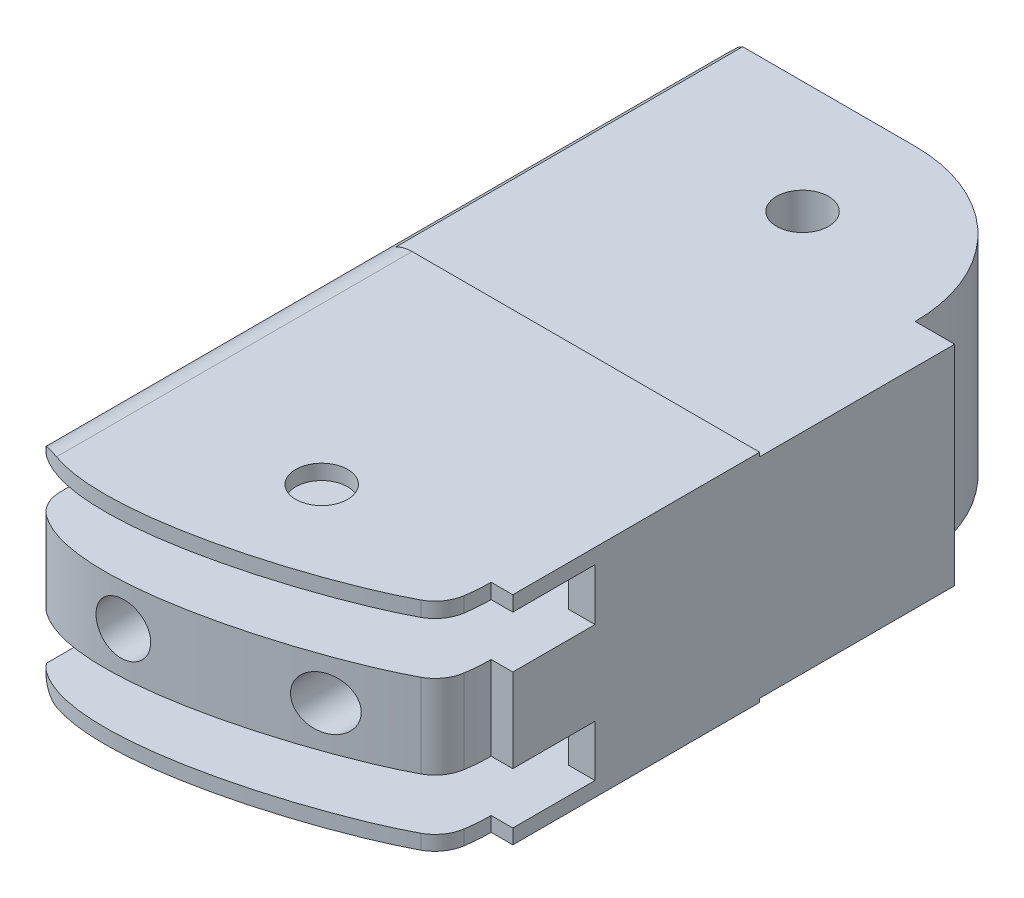
SolidWorks part; units mm, degrees
ref_plane "Front Plane" through (0, 0, 0) normal (0, 0, 1) x (1, 0, 0)
ref_plane "Top Plane" through (0, 0, 0) normal (0, 1, 0) x (1, 0, 0)
ref_plane "Right Plane" through (0, 0, 0) normal (1, 0, 0) x (0, 0, -1)
sketch "Sketch1" plane through (0, 0, 0) normal (0, 0, 1) x (1, 0, 0)
  line L0 (-24.2561, -24.0702) -> (-22.0061, -24.0702) construction
  line L1 (-24.2561, -17.8202) -> (-2.2017, -17.8202)
  line L2 (-24.2561, -17.8202) -> (-24.2561, -30.3202)
  line L3 (-24.2561, -30.3202) -> (-2.2017, -30.3202)
  line L4 (-2.2017, -17.8202) -> (-2.2017, -30.3202)
  line L5 (-2.2017, -24.0702) -> (-4.4517, -24.0702) construction
  line L6 (-22.0061, -24.0702) -> (-22.0061, -30.3202) construction
  line L7 (-4.4517, -24.0702) -> (-4.4517, -30.3202) construction
extrude "Boss-Extrude1" add sketch "Sketch1" along normal blind 43
sketch "Sketch2" plane through (0, -30.3202, 0) normal (0, -1, 0) x (1, 0, 0)
  line L0 (-3.4524, 34.2429) -> (-2.2017, 34.2429)
  line L1 (-24.2561, 0) -> (-2.2017, 0) construction
  line L2 (-13.2289, 0) -> (-13.2289, 8.75) construction
  line L4 (-24.2561, 43) -> (-24.2561, 0) construction
  line L5 (-4.4789, 8.75) -> (-2.2017, 8.75)
  line L6 (-2.2017, 43) -> (-2.2017, 0) construction
  line L7 (-13.2289, 43) -> (-13.2289, 34.2429) construction
  line L8 (-24.2561, 43) -> (-2.2017, 43) construction
  line L11 (-13.2289, 8.75) -> (-13.2289, 6.5) construction
  line L12 (-24.2561, 0) -> (-2.2017, 0) construction
  arc A1 (-13.2289, 0) -> (-4.4789, 8.75) centre (-13.2289, 8.75) ccw
  circle A4 centre (-13.2289, 6.5) radius 1.5
  arc A6 (-3.4524, 34.2429) -> (-3.7578, 36.6675) centre (-13.2289, 34.2429) ccw
  circle A7 centre (-13.2289, 34.2429) radius 1.5
  spline S0 degree 3 poles (-2.2017, 8.75) (5.3921, 3.8803) (-0.7771, -4.5233) (-17.1743, -10.6233) (-34.8214, -0.026) (-24.2561, 8.75) knots 0 0 0 0 0.283273 0.504245 1 1 1 1
  spline S1 degree 3 poles (-24.2561, 33.8451) (-30.5755, 43.6074) (-11.1959, 55.0124) (11.4737, 42.1354) (-2.2017, 34.2429) knots 0 0 0 0 0.486113 1 1 1 1
  spline S2 degree 1 poles (-13.2289, 0) (-23.4906, 0) knots 0 0 1 1
  spline S3 degree 2 poles (-23.4906, 0) (-24.9665, 4.2378) (-24.2561, 8.75) knots 0 0 0 1 1 1
  spline S4 degree 3 poles (-3.7578, 36.6675) (-8.0593, 39.5101) (-28.6882, 46.07) (-24.2561, 33.8451) knots 0 0 0 0 1 1 1 1
extrude "Cut-Extrude1" cut sketch "Sketch2" against normal blind 15 and the other way blind 10
fillet "Fillet3" radius 2 4 edges at (-24.2561, -17.8202, 21.0415) (-24.2561, -30.3202, 21.0415) (-24.2561, -24.0702, 3.0015) (-24.2561, -24.0702, 39.0815)
ref_plane "Plane1" through (0, 0, 0) normal (0, 0, 1) x (1, 0, 0)
sketch "Sketch5" plane through (0, 0, 0) normal (0, 0, 1) x (1, 0, 0)
  line L0 (-2.2017, -24.0702) -> (-8.4468, -24.0702) construction
  line L1 (-2.2017, -30.3202) -> (-24.2561, -30.3202) construction
  line L2 (-2.2017, -30.3202) -> (-2.2017, -17.8202) construction
  line L3 (-2.2017, -17.8202) -> (-24.2561, -17.8202) construction
  line L4 (-24.2561, -30.3202) -> (-24.2561, -17.8202) construction
  line L5 (-24.2561, -24.0702) -> (-18.0111, -24.0702) construction
  circle A0 centre (-18.0111, -24.0702) radius 1.5
  circle A1 centre (-8.4468, -24.0702) radius 1.5
extrude "Cut-Extrude4" cut sketch "Sketch5" along normal through all
ref_plane "Plane5" through (0, 0, 38) normal (0, 0, 1) x (1, 0, 0)
sketch "Sketch16" plane through (0, 0, 38) normal (0, 0, 1) x (1, 0, 0)
  line L0 (-2.9534, -17.6304) -> (-2.1067, -18.6895) construction
  line L1 (-2.9534, -17.6304) -> (-24.3617, -17.6304) construction
  line L3 (-2.1067, -30.8303) -> (-24.3617, -30.8303) construction
  line L4 (-24.3617, -17.6304) -> (-24.3617, -30.8303) construction
  line L5 (-2.9534, -17.6304) -> (-24.3617, -30.8303) construction
  line L6 (-2.1067, -30.8303) -> (-24.3617, -17.6304) construction
  line L7 (-2.1067, -30.8303) -> (-2.1067, -29.4743) construction
  line L8 (-13.2342, -21.681) -> (-13.2342, -24.2303) construction
  line L9 (-2.1067, -18.6895) -> (-24.3617, -18.6895)
  line L10 (-2.1067, -18.6895) -> (-2.1067, -21.681)
  line L11 (-2.1067, -21.681) -> (-24.3617, -21.681)
  line L12 (-24.3617, -18.6895) -> (-24.3617, -21.681)
  line L13 (-2.1067, -18.6895) -> (-24.3617, -21.681) construction
  line L14 (-2.1067, -21.681) -> (-24.3617, -18.6895) construction
  line L15 (-2.1067, -29.4743) -> (-24.3617, -29.4743)
  line L16 (-2.1067, -29.4743) -> (-2.1067, -26.5118)
  line L17 (-2.1067, -26.5118) -> (-24.3617, -26.5118)
  line L18 (-24.3617, -29.4743) -> (-24.3617, -26.5118)
  line L19 (-2.1067, -29.4743) -> (-24.3617, -26.5118) construction
  line L20 (-2.1067, -26.5118) -> (-24.3617, -29.4743) construction
  line L21 (-13.2342, -24.2303) -> (-13.2342, -26.5118) construction
  point P4 (-13.45, -24.1024)
  point P10 (-13.2342, -20.1852)
  point P14 (-13.2342, -27.9931)
extrude "Cut-Extrude6" cut sketch "Sketch16" against normal blind 8.5 and the other way blind 10
fillet "Fillet4" radius 2 3 edges at (-3.7578, -18.2549, 36.6675) (-3.7578, -24.0964, 36.6675) (-3.7578, -29.8973, 36.6675)
sketch "Sketch17" plane through (0, 0, 29.5) normal (0, 0, 1) x (1, 0, 0)
  line L0 (-23.8895, -29.4743) -> (-2.2017, -29.4743) construction
  line L1 (-3.7336, -29.4743) -> (-22.3537, -29.4743)
  line L2 (-3.7336, -29.4743) -> (-3.7336, -26.5118)
  line L3 (-3.7336, -26.5118) -> (-22.3537, -26.5118)
  line L4 (-22.3537, -29.4743) -> (-22.3537, -26.5118)
  line L5 (-3.7336, -29.4743) -> (-22.3537, -26.5118) construction
  line L6 (-3.7336, -26.5118) -> (-22.3537, -29.4743) construction
  line L7 (-2.2017, -26.5118) -> (-24.2561, -26.5118) construction
  line L8 (-24.2561, -21.681) -> (-2.2017, -21.681) construction
  line L9 (-22.3537, -21.681) -> (-3.7336, -21.681)
  line L10 (-22.3537, -21.681) -> (-22.3537, -18.6895)
  line L11 (-22.3537, -18.6895) -> (-3.7336, -18.6895)
  line L12 (-3.7336, -21.681) -> (-3.7336, -18.6895)
  line L13 (-22.3537, -21.681) -> (-3.7336, -18.6895) construction
  line L14 (-22.3537, -18.6895) -> (-3.7336, -21.681) construction
  line L15 (-2.2017, -18.6895) -> (-23.9059, -18.6895) construction
  point P4 (-13.0437, -27.9931)
  point P13 (-13.0437, -20.1852)
extrude "Cut-Extrude7" cut sketch "Sketch17" against normal blind 5
sketch "Sketch18" plane through (0, 0, 0) normal (0, 0, 1) x (1, 0, 0)
  line L1 (-1.4538, -30.6251) -> (-25.2697, -30.6251)
  line L2 (-1.4538, -30.6251) -> (-1.4538, -30.1164)
  line L3 (-1.4538, -30.1164) -> (-25.2697, -30.1164)
  line L4 (-25.2697, -30.6251) -> (-25.2697, -30.1164)
  line L5 (-1.4538, -30.6251) -> (-25.2697, -30.1164) construction
  line L6 (-1.4538, -30.1164) -> (-25.2697, -30.6251) construction
  line L7 (-1.4538, -18.0491) -> (-25.2729, -18.0491)
  line L8 (-1.4538, -18.0491) -> (-1.4538, -17.3801)
  line L9 (-1.4538, -17.3801) -> (-25.2729, -17.3801)
  line L10 (-25.2729, -18.0491) -> (-25.2729, -17.3801)
  line L11 (-1.4538, -18.0491) -> (-25.2729, -17.3801) construction
  line L12 (-1.4538, -17.3801) -> (-25.2729, -18.0491) construction
  point P4 (-13.3617, -30.3707)
  point P9 (-13.3634, -17.7146)
  point P10 (-25.2697, -30.1164)
  point P11 (-25.2729, -18.0491)
extrude "Cut-Extrude8" cut sketch "Sketch18" along normal blind 20
